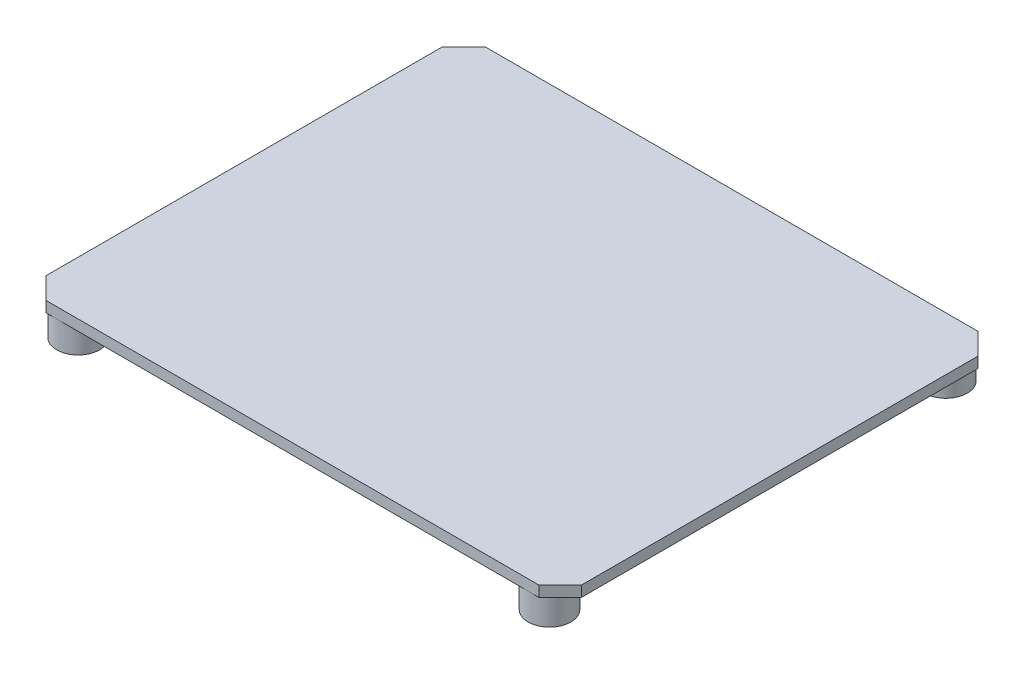
SolidWorks part; units mm, degrees
ref_plane "Front Plane" through (0, 0, 0) normal (0, 0, 1) x (1, 0, 0)
ref_plane "Top Plane" through (0, 0, 0) normal (0, 1, 0) x (1, 0, 0)
ref_plane "Right Plane" through (0, 0, 0) normal (1, 0, 0) x (0, 0, -1)
ref_plane "PZ33_4" through (0, 33.4, 0) normal (0, 1, 0) x (1, 0, 0)
sketch "Sketch1" plane through (0, 33.4, 0) normal (0, 1, 0) x (1, 0, 0)
  line L0 (-46, -102) -> (46, -102)
  line L1 (46, -102) -> (50, -98)
  line L2 (50, -98) -> (50, -24)
  line L3 (50, -24) -> (46, -20)
  line L4 (46, -20) -> (-46, -20)
  line L5 (-46, -20) -> (-50, -24)
  line L6 (-50, -24) -> (-50, -98)
  line L7 (-50, -98) -> (-46, -102)
extrude "Shade Plate" add sketch "Sketch1" along normal blind 2
ref_plane "PZ28_4" through (0, 28.4, 0) normal (0, 1, 0) x (1, 0, 0)
sketch "Sketch2" plane through (0, 28.4, 0) normal (0, 1, 0) x (1, 0, 0)
  circle A0 centre (-44, -24) radius 4
  circle A1 centre (-44, -98) radius 4
  circle A2 centre (44, -24) radius 4
  circle A3 centre (44, -98) radius 4
extrude "Posts" add sketch "Sketch2" along normal blind 5.1
ref_plane "PZ27_9" through (0, 27.9, 0) normal (0, 1, 0) x (1, 0, 0)
sketch "Sketch3" plane through (0, 27.9, 0) normal (0, 1, 0) x (1, 0, 0)
  circle A0 centre (-44, -24) radius 1.25
  circle A1 centre (-44, -98) radius 1.25
  circle A2 centre (44, -24) radius 1.25
  circle A3 centre (44, -98) radius 1.25
extrude "Post Pilots" cut sketch "Sketch3" along normal blind 6.5
equation "\"BOARD_REAR\" = 86.0"
equation "\"BOARD_FRONT\" = 41.0"
equation "\"BOARD_END\" = 22.0"
equation "\"BOARD_ANGLED\" = 30.0"
equation "\"BOARD_DEPTH\" = 41.8431"
equation "\"PCB_T\" = 1.6"
equation "\"ABOVE_PCB\" = 14.0"
equation "\"BELOW_PCB\" = 6.0"
equation "\"MID_PARTS_H\" = 9.0"
equation "\"BOARD_HOLE_PILOT\" = 1.6"
equation "\"J2_X\" = 19.0"
equation "\"DUPONT_DROP\" = 14.0"
equation "\"BEND_R\" = 5.0"
equation "\"BOARD_GAP\" = 3.0"
equation "\"TOF_FOV\" = 25.0"
equation "\"TOF_MARGIN_DEG\" = 5.0"
equation "\"TOF_WIN_MARGIN\" = 1.0"
equation "\"TOF_Z\" = 9.0"
equation "\"TOF_SIDE_BEARING\" = 90.0"
equation "\"TOF_CONE_LEN\" = 70.0"
equation "\"CAM_W\" = 29.2"
equation "\"CAM_H\" = 28.2"
equation "\"CAM_D\" = 12.35"
equation "\"CAM_FRONT_Y\" = 43.0"
equation "\"CAM_BOTTOM_Z\" = 17.0"
equation "\"CAM_LENS_UP\" = 11.6"
equation "\"CAM_LENS_OPEN\" = 9.6"
equation "\"CAM_HFOV\" = 53.5"
equation "\"CAM_VFOV\" = 41.41"
equation "\"CAM_FOV_MARGIN\" = 3.0"
equation "\"CAM_FIT\" = 0.3"
equation "\"RIBBON_W\" = 16.0"
equation "\"RIBBON_T\" = 0.3"
equation "\"RIBBON_LEN\" = 150.0"
equation "\"RIBBON_EXIT_Y\" = 35.0"
equation "\"WALL\" = 2.4"
equation "\"HEAD_X\" = 48.4"
equation "\"HEAD_REAR_Y\" = -11.9"
equation "\"CAM_FOAM\" = 2.8"
equation "\"HEAD_FRONT_Y\" = 48.2"
equation "\"HEAD_TOP_Z\" = 50.6"
equation "\"HEAD_BOT_Z\" = -28.4"
equation "\"HEAD_SPLIT_Z\" = -4.0"
equation "\"SKIRT_T\" = 1.2"
equation "\"SKIRT_H\" = 3.0"
equation "\"SKIRT_FIT\" = 0.3"
equation "\"VISOR\" = 7.8"
equation "\"VISOR_Z\" = 40.0"
equation "\"ROOF_SLOPE_Y\" = 40.0"
equation "\"ROOF_CHAMFER\" = 10.0"
equation "\"REAR_CHAMFER\" = 10.0"
equation "\"CORNER_CHAMFER\" = 6.0"
equation "\"LOWER_SIDE_FACET\" = 6.0"
equation "\"LIGHTBAR_DEPTH\" = 1.0"
equation "\"HOOD_Z\" = 14.0"
equation "\"HOOD_L\" = 6.0"
equation "\"SIDE_HOOD_L\" = 4.0"
equation "\"INSERT_M3_D\" = 4.0"
equation "\"INSERT_M3_L\" = 6.0"
equation "\"M3_CLEAR\" = 3.4"
equation "\"M2_PILOT\" = 1.6"
equation "\"M25_PILOT\" = 2.2"
equation "\"BOX_X\" = 72.4"
equation "\"BOX_FRONT_Y\" = -11.9"
equation "\"BOX_REAR_Y\" = -124.4"
equation "\"BOX_BOT_Z\" = -28.4"
equation "\"BOX_TOP_Z\" = 26.0"
equation "\"LID_T\" = 2.4"
equation "\"LID_SKIRT\" = 1.6"
equation "\"LID_TONGUE_H\" = 3.0"
equation "\"LID_FIT\" = 0.3"
equation "\"PI_STANDOFF\" = 8.0"
equation "\"BOX_REAR_CHAMFER\" = 8.0"
equation "\"BOX_REAR_FACET\" = 4.0"
equation "\"VENT_UPSTAND\" = 3.0"
equation "\"TUBE_D\" = 22.2"
equation "\"TUBE_LINER\" = 1.0"
equation "\"MOUNT_Y\" = -70.0"
equation "\"RAIL_W\" = 30.0"
equation "\"RAIL_W2\" = 38.0"
equation "\"RAIL_H\" = 6.0"
equation "\"SLIDE\" = 0.3"
equation "\"STOP_T\" = 6.0"
equation "\"CLAMP_W\" = 40.0"
equation "\"CLAMP_HALF\" = 20.0"
equation "\"CLAMP_DROP\" = 12.0"
equation "\"CAP_T\" = 12.0"
equation "\"CLAMP_BOLT_OFF\" = 16.6"
equation "\"M5_INSERT_D\" = 6.4"
equation "\"M5_CLEAR\" = 5.5"
equation "\"LOCK_D\" = 3.3"
equation "\"POD_TILT_DEG\" = 0.0"
equation "\"PRINT_LIMIT\" = 180.0"
equation "\"PI5_L\" = 85.0"
equation "\"PI5_W\" = 56.0"
equation "\"PI5_T\" = 1.6"
equation "\"PI5_USBC_BX\" = 11.2"
equation "\"PI5_ETH_BY\" = 10.2"
equation "\"PI5_PORT_OVERHANG\" = 3.0"
equation "\"PI5_FPC_H\" = 5.0"
equation "\"PI5_FPC_USE\" = 0.0"
equation "\"PI5_PIN1_BX\" = 8.37"
equation "\"HEADER_BASE_H\" = 2.5"
equation "\"DUPONT_L\" = 14.0"
equation "\"PI5_UNDERSIDE\" = 1.5"
equation "\"COOLER_H\" = 15.0"
equation "\"HAT_W\" = 65.0"
equation "\"HAT_D\" = 56.5"
equation "\"HAT_T\" = 1.6"
equation "\"HAT_SPACER\" = 16.0"
equation "\"HAILO_H\" = 10.0"
equation "\"STACK_PINS_H\" = 6.0"
equation "\"DUPONT_SEAT\" = 0.5"
equation "\"PCIE_FFC_LOOP\" = 6.0"
equation "\"HAILO_AIR_GAP_MIN\" = 8.0"
equation "\"M25_CLEAR\" = 2.7"
equation "\"PI_X0\" = -55.0"
equation "\"PI_Y1\" = -36.5"
equation "\"PI_Y0\" = -92.5"
equation "\"BOX_LEN\" = 112.5"
equation "\"COVER_T\" = 3.0"
equation "\"COVER_TOP_Z\" = 6.5"
equation "\"SIDE_LEDGE_Z\" = -2.5"
equation "\"UPPER_LEDGE_Z\" = 15.5"
equation "\"REAR_LEDGE_Z\" = 8.0"
equation "\"LEDGE_L\" = 4.0"
equation "\"RIBBON_W_PI\" = 11.5"
equation "\"RIBBON_RUN_Z\" = 12.0"
equation "\"RIBBON_SPEC_LEN\" = 200.0"
